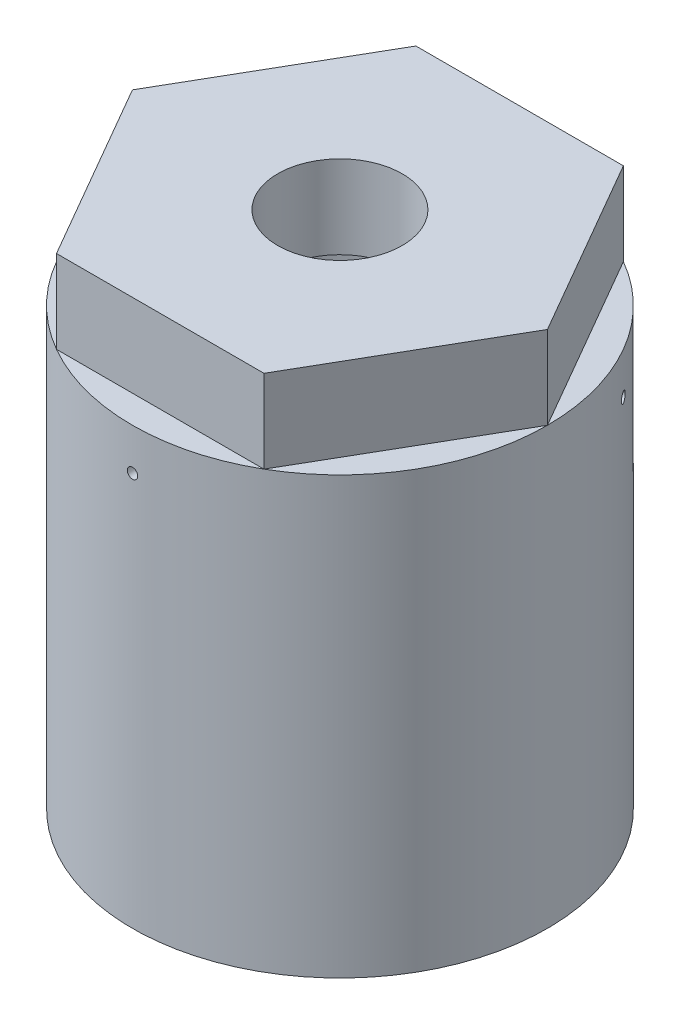
SolidWorks part; units mm, degrees
material "6061-T6 (SS)"
ref_plane "Piano frontale" through (0, 0, 0) normal (0, 0, 1) x (1, 0, 0)
ref_plane "Piano superiore" through (0, 0, 0) normal (0, 1, 0) x (1, 0, 0)
ref_plane "Piano destro" through (0, 0, 0) normal (1, 0, 0) x (0, 0, -1)
sketch "Schizzo1" plane through (0, 0, 0) normal (0, 0, 1) x (1, 0, 0)
  line L0 (0, 0) -> (0, 23.6846) construction
  line L1 (-14, 0) -> (-14, 30)
  line L2 (-14, 30) -> (0, 30)
  line L3 (0, 30) -> (0, 38)
  line L4 (0, 38) -> (-20, 38)
  line L5 (-20, 38) -> (-20, 0)
  line L6 (-20, 0) -> (-14, 0)
  line L7 (-20, 0) -> (-20, -12)
  line L8 (-20, -12) -> (-18, -12)
  line L9 (-18, 0) -> (-18, -12) construction
  line L10 (-18, -12) -> (-18, 0)
  line L11 (-18, 0) -> (-18, -12) construction
  line L12 (-15, 0) -> (-15, 5)
  line L13 (-15, 5) -> (-14, 6)
  dimension "D1" = 28
  dimension "D2" = 40
  dimension "D3" = 8
  dimension "D4" = 30
  dimension "D5" = 12
  dimension "D6" = 1
  dimension "D7" = 5
  dimension "D8" = 45
revolve "Rivoluzione1" add sketch "Schizzo1" angle 360 about L0 region at (-14.8036, 5.8036, 0) region at (-19, -6, 0)
sketch "Schizzo2" plane through (0, 38, 0) normal (0, 1, 0) x (1, 0, 0)
  circle A0 centre (0, 0) radius 6
  dimension "D1" = 12
extrude "Taglio-Estrusione1" cut sketch "Schizzo2" against normal blind 11
ref_plane "Piano1" through (0, 0, 20) normal (0, 0, 1) x (1, 0, 0)
sketch "Schizzo3" plane through (0, 0, 20) normal (0, 0, 1) x (1, 0, 0)
  circle A0 centre (0, 26) radius 0.5
  point P2 (0, 0)
  point P5 (0, 0)
  dimension "D1" = 1
  dimension "D2" = 26
extrude "Taglio-Estrusione2" cut sketch "Schizzo3" against normal blind 10
pattern_circular "RipetizioneCircolare1" count 3 over 360 about axis through (0, 38, 0) along (0, -1, 0) of "Taglio-Estrusione2"
sketch "Schizzo4" plane through (0, 38, 0) normal (0, 1, 0) x (1, 0, 0)
  line L0 (-10, 17.3205) -> (-20, 0)
  line L1 (-20, 0) -> (-10, -17.3205)
  line L2 (-10, -17.3205) -> (10, -17.3205)
  line L3 (10, -17.3205) -> (20, 0)
  line L4 (20, 0) -> (10, 17.3205)
  line L5 (10, 17.3205) -> (-10, 17.3205)
  circle A0 centre (0, 0) radius 20 construction
  circle A3 centre (0, 0) radius 20
  circle M9 centre (0, 0) radius 20
fillet "Raccordo1" radius 0.5 1 edges at (0, 30, -14)
extrude "Taglio-Estrusione3" cut sketch "Schizzo4" against normal blind 8 contours L0 M9 | L1 M9 | L2 M9 | L3 M9 | L4 M9 | L5 M9 region at (0, 38, -18.3987) region at (-15.9337, 38, -9.1994) region at (-15.9337, 38, 9.1994) region at (15.9337, 38, -9.1994) region at (0, 38, 18.3987) region at (15.9337, 38, 9.1994)
